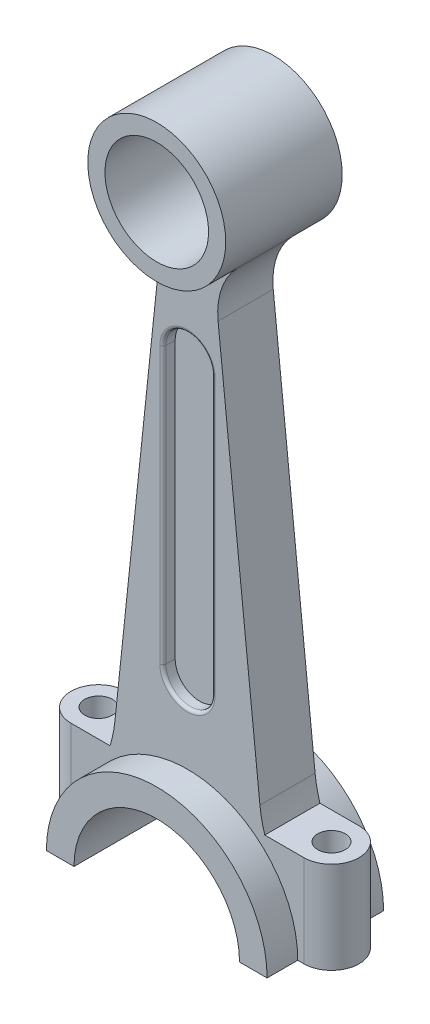
SolidWorks part; units mm, degrees
ref_plane "Front Plane" through (0, 0, 0) normal (0, 0, 1) x (1, 0, 0)
ref_plane "Top Plane" through (0, 0, 0) normal (0, 1, 0) x (1, 0, 0)
ref_plane "Right Plane" through (0, 0, 0) normal (1, 0, 0) x (0, 0, -1)
sketch "Sketch1" plane through (0, 0, 0) normal (0, 0, 1) x (1, 0, 0)
  line L0 (0, 0) -> (0, 49693.6393) construction
  line L1 (0, 0) -> (49693.6393, 0) construction
  line L2 (10, 167.5952) -> (23.6553, 37.674)
  line L3 (-10, 167.5952) -> (-23.6553, 37.674)
  line L4 (0, 151.2) -> (0, 61.2) construction
  line L5 (8, 151.2) -> (8, 61.2)
  line L6 (-8, 151.2) -> (-8, 61.2)
  line L7 (27, 0) -> (47, 0)
  line L8 (47, 0) -> (47, 30)
  line L9 (47, 30) -> (19.8997, 30)
  line L10 (-27, 0) -> (-47, 0)
  line L11 (-47, 30) -> (-19.8997, 30)
  line L12 (-47, 0) -> (-47, 30)
  arc A0 (-36, 0) -> (36, 0) centre (0, 0) cw
  arc A1 (-27, 0) -> (27, 0) centre (0, 0) cw
  circle A2 centre (0, 201.2) radius 22.5
  circle A3 centre (0, 201.2) radius 16.9
  arc A4 (23.6553, 37.674) -> (30.0487, 19.8261) centre (63.4361, 41.8552) ccw
  arc A5 (10, 167.5952) -> (16.1884, 185.5735) centre (32.3767, 169.9471) cw
  arc A6 (-23.6553, 37.674) -> (-30.0487, 19.8261) centre (-63.4361, 41.8552) cw
  arc A7 (-10, 167.5952) -> (-16.1884, 185.5735) centre (-32.3767, 169.9471) ccw
  arc A8 (8, 151.2) -> (-8, 151.2) centre (0, 151.2) ccw
  arc A9 (-8, 61.2) -> (8, 61.2) centre (0, 61.2) ccw
  point P27 (0, 106.2)
  dimension "D1" = 45
  dimension "D2" = 33.8
  dimension "D3" = 36
  dimension "D4" = 27
  dimension "D6" = 22.5
  dimension "D7" = 40
  dimension "D11" = 8
  dimension "D5" = 201.2
  dimension "D8" = 20
  dimension "D9" = 90
  dimension "D10" = 50
  dimension "D12" = 6
  dimension "D13" = 30
  dimension "D14" = 47
extrude "Boss-Extrude1" add sketch "Sketch1" along normal mid plane 38 contours A2 A3 | L10 A1 L7 A0 region at (0, 179.3364, 0) region at (24.9171, 24.8561, 0)
extrude "Boss-Extrude2" add sketch "Sketch1<3>" along normal mid plane 18 contours A7 L3 A6 L11 A0 L9 A4 L2 A5 A2 A9 L6 A8 L5 region at (15.201, 102.4636, 0)
sketch "Sketch1<3>" plane through (0, 0, 0) normal (0, 0, 1) x (1, 0, 0) same geometry as "Sketch1"
extrude "Boss-Extrude3" add sketch "Sketch1<4>" along normal mid plane 18 contours L9 A4 A0 L7 L8 | A4 L9 A0 | L11 A6 A0 | A6 L11 L12 L10 A0 region at (24.5888, 27.5185, 0) region at (38.9776, 17.0008, 0) region at (-24.5888, 27.5185, 0) region at (-38.9776, 17.0008, 0)
sketch "Sketch1<4>" plane through (0, 0, 0) normal (0, 0, 1) x (1, 0, 0) same geometry as "Sketch1"
fillet "Fillet1" 2 edges at (-47, 15, 9) (-47, 15, -9) type full round first side face at (0, 106.2, 9) second side face at (0, 106.2, -9) middle face at (-47, 15, 0)
fillet "Fillet2" 2 edges at (47, 15, 9) (47, 15, -9) type full round first side face at (0, 106.2, 9) second side face at (0, 106.2, -9) middle face at (47, 15, 0)
extrude "Boss-Extrude4" add sketch "Sketch1<5>" along normal mid plane 10 contours L6 A9 L5 A8 region at (0, 106.2, 0)
sketch "Sketch1<5>" plane through (0, 0, 0) normal (0, 0, 1) x (1, 0, 0) same geometry as "Sketch1"
fillet "Fillet3" radius 1 8 edges at (0, 159.2, 9) (8, 106.2, 9) (0, 53.2, 9) (0, 159.2, -9) (8, 106.2, -9) (0, 53.2, -9) (-8, 106.2, 9) (-8, 106.2, -9)
hole_wizard "M10x1.5 Tapped Hole1" positions "Sketch2" profile "Sketch3" tap size "M10x1.5" standard "ANSI Metric" end condition up to next
sketch "Sketch2" plane through (0, 0, 0) normal (0, -1, 0) x (-1, 0, 0)
  point P0 (-38, 0)
  point P3 (38, 0)
sketch "Sketch3" plane through (38, 0, 0) normal (1, 0, 0) x (0, 0, -1)
  line L0 (0, 0) -> (0, 30)
  line L1 (0, 30) -> (4.5, 30)
  line L2 (4.5, 30) -> (4.5, 0)
  line L5 (4.5, 0) -> (0, 0)
  line L11 (0, -6.35) -> (0, 107.95) construction
  dimension "Thru Tap Drill Dia." = 9
  dimension "Thru Tap Drill Depth" = 30
cosmetic thread "Hole Thread1" parameters "D2"=10
cosmetic thread "Hole Thread2" parameters "D2"=10
